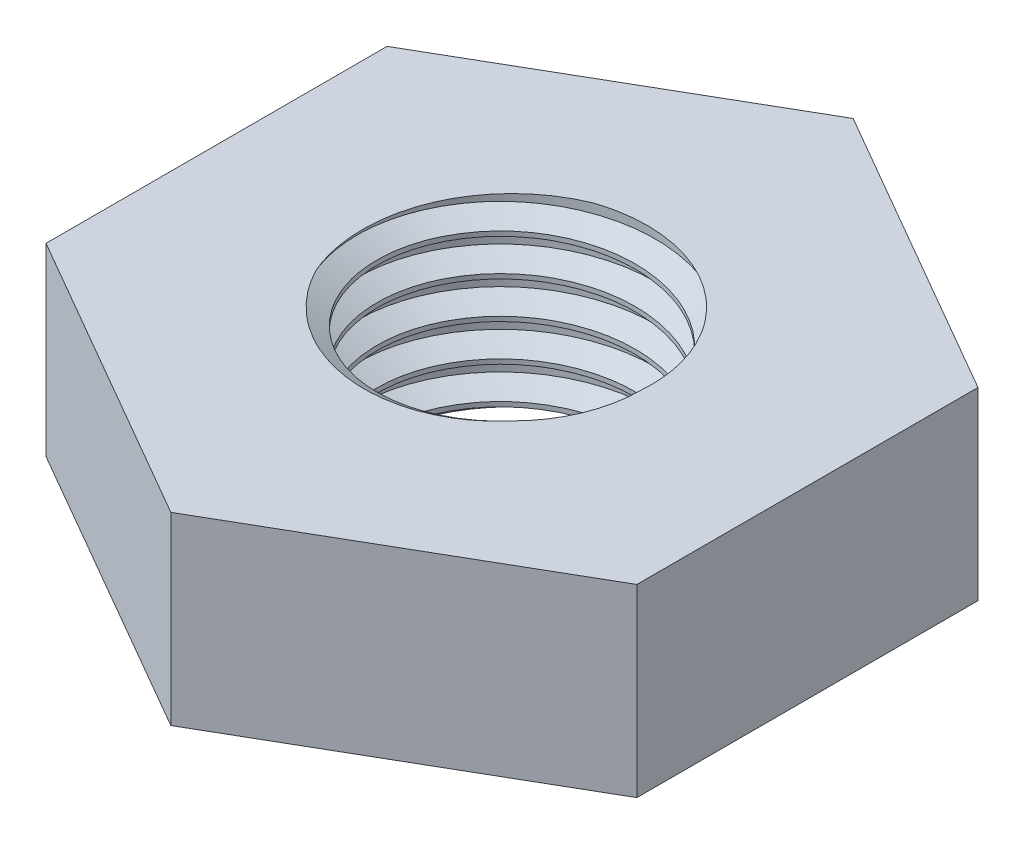
SolidWorks part; units mm, degrees
ref_plane "Front Plane" through (0, 0, 0) normal (0, 0, 1) x (1, 0, 0)
ref_plane "Top Plane" through (0, 0, 0) normal (0, 1, 0) x (1, 0, 0)
ref_plane "Right Plane" through (0, 0, 0) normal (1, 0, 0) x (0, 0, -1)
sketch "Sketch1" plane through (0, 0, 0) normal (0, 1, 0) x (1, 0, 0)
  line L1 (0, 18.4752) -> (-16, 9.2376)
  line L2 (-16, 9.2376) -> (-16, -9.2376)
  line L3 (-16, -9.2376) -> (0, -18.4752)
  line L4 (0, -18.4752) -> (16, -9.2376)
  line L5 (16, -9.2376) -> (16, 9.2376)
  line L6 (16, 9.2376) -> (0, 18.4752)
  circle A0 centre (0, 0) radius 16 construction
  point P1 (0, 0)
  dimension "D1" = 32
extrude "Boss-Extrude1" add sketch "Sketch1" along normal mid plane 10
hole_wizard "M16x2.0 Tapped Hole1" positions "Sketch2" profile "Sketch3" tap size "M16x2.0" standard "ANSI Metric" end condition through all
sketch "Sketch2" plane through (0, 5, 0) normal (0, 1, 0) x (1, 0, 0)
  point P0 (0, 0)
sketch "Sketch3" plane through (0, 5, 0) normal (1, 0, 0) x (0, 0, 1)
  line L0 (0, 0) -> (0, 10)
  line L1 (0, 10) -> (7, 10)
  line L2 (7, 10) -> (7, 0)
  line L5 (7, 0) -> (0, 0)
  line L11 (0, -6.35) -> (0, 107.95) construction
  dimension "Thru Tap Drill Dia." = 14
  dimension "Thru Tap Drill Depth" = 10
cosmetic thread "Hole Thread1" parameters "D2"=16
thread "Thread1" pitch 2 method cut profile "Thread Profile1" start angle 0, offset 3, length 38, pitch 2, diameter 14
ref_plane "Plane1" through (-7, 8, 0) normal (0, 0, -1) x (1, 0, 0)
sketch "Thread Profile1" plane through (-7, 8, 0) normal (0, 0, -1) x (1, 0, 0)
  line L0 (0, 0) -> (0, 2) construction
  line L11 (0, 0) -> (0, 1.75)
  line L12 (0, 1.75) -> (-1.0825, 1.125)
  line L13 (-1.0825, 1.125) -> (-1.0825, 0.625)
  line L15 (-1.0825, 0.625) -> (0, 0)
  line L17 (-1.0825, 0.875) -> (0, 0.875) construction
  point P2 (0, 0)
  dimension "Pitch" = 2
  dimension "Profile_Angle" = 60
  dimension "Profile_Land" = 0.5
  dimension "Profile_Height" = 1.0825
